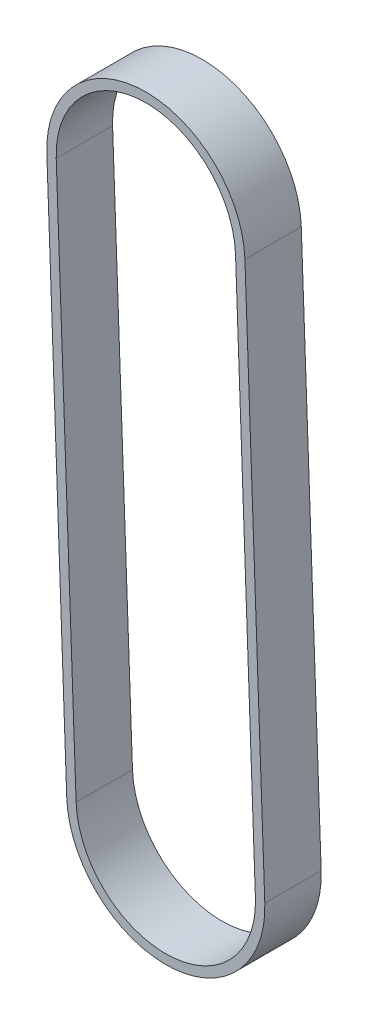
SolidWorks part; units mm, degrees
ref_plane "Front Plane" through (0, 0, 0) normal (0, 0, 1) x (1, 0, 0)
ref_plane "Top Plane" through (0, 0, 0) normal (0, 1, 0) x (1, 0, 0)
ref_plane "Right Plane" through (0, 0, 0) normal (1, 0, 0) x (0, 0, -1)
sketch "Sketch2" plane through (0, 0, 0) normal (0, 0, 1) x (1, 0, 0)
  line L0 (0, 0) -> (1, 0) construction
  line L1 (0, 0) -> (0, 1) construction
  line L4 (13.846, 0.8248) -> (17.021, -86.6176)
  line L5 (-11.608, -87.6571) -> (-14.783, -0.2147)
  arc A0 (-14.783, -0.2147) -> (13.846, 0.8248) centre (-0.4685, 0.305) cw
  arc A2 (17.021, -86.6176) -> (-11.608, -87.6571) centre (2.7065, -87.1374) cw
extrude "Extrude-Thin1" add sketch "Sketch2" against normal blind 9 thin thin type one direction wall 1.5
